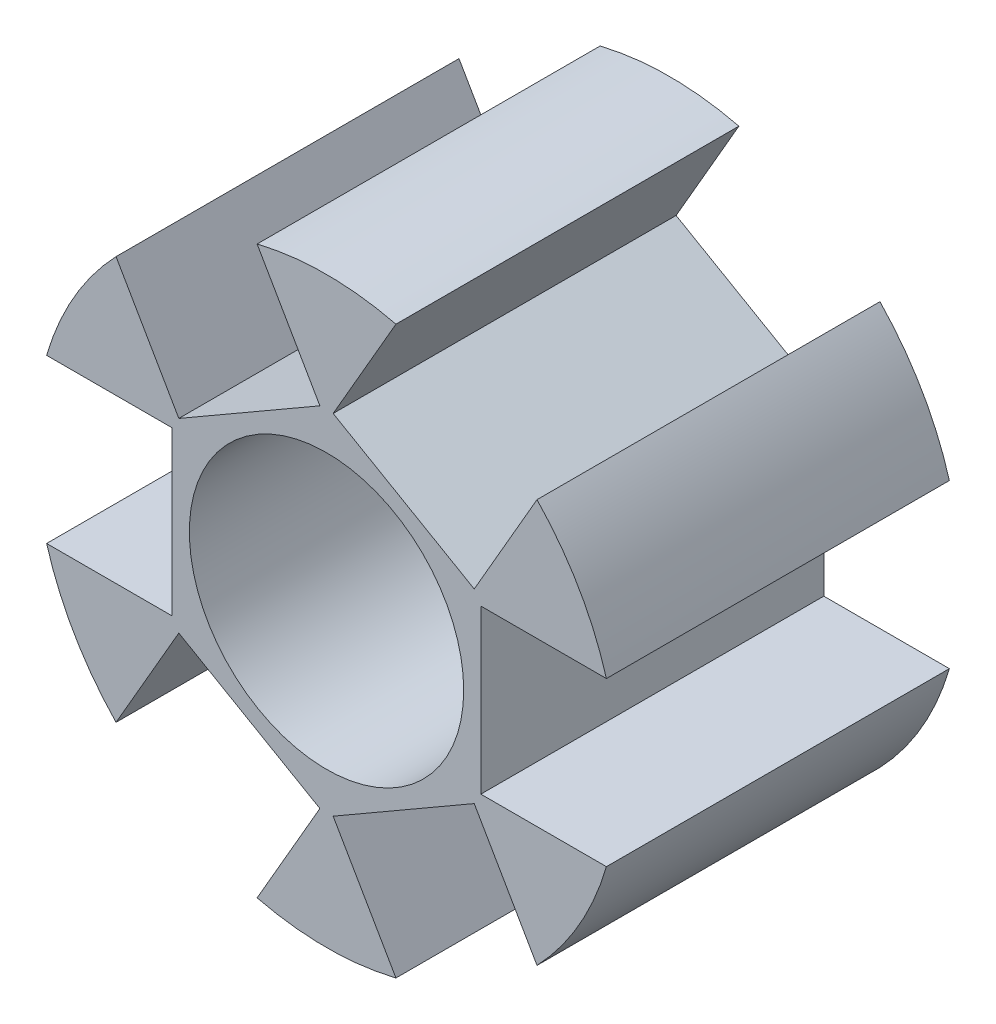
SolidWorks part; units mm, degrees
ref_plane "Top Plane" through (0, 0, 0) normal (0, 0, 1) x (1, 0, 0)
ref_plane "Right Plane" through (0, 0, 0) normal (0, 1, 0) x (1, 0, 0)
ref_plane "Front Plane" through (0, 0, 0) normal (1, 0, 0) x (0, 0, -1)
ref_axis "x-axis" through (-88.99, 0, 0) along (1, 0, 0)
ref_axis "y-axis" through (0, -55, 0) along (0, 1, 0)
ref_axis "z-axis" through (0, 0, 55) along (0, 0, -1)
sketch "Sketch1" plane through (0, 0, 0) normal (0, 0, 1) x (1, 0, 0)
  line L8 (-19.9785, 0) -> (0, 0) construction
  line L16 (0, 0) -> (0, -20.7846) construction
  line L23 (0, 0) -> (0, -20.7846) construction
  circle A0 centre (0, 0) radius 4
  circle A3 centre (0, 0) radius 8.5
  dimension "D1" = 8
  dimension "D2" = 17
extrude "Boss-Extrude1" add sketch "Sketch1" along normal mid plane 10
ref_plane "Plane1" through (-8.5, 0, 0) normal (-1, 0, 0) x (0, 0, 1)
sketch "Sketch2" plane through (-8.5, -17.1931, 0) normal (1, 0, 0) x (0, -1, 0)
  line L1 (-19.5681, -5) -> (-14.8181, -5)
  line L2 (-19.5681, -5) -> (-19.5681, 5)
  line L3 (-19.5681, 5) -> (-14.8181, 5)
  line L4 (-14.8181, -5) -> (-14.8181, 5)
  line L5 (-19.5681, -5) -> (-14.8181, 5) construction
  line L6 (-19.5681, 5) -> (-14.8181, -5) construction
  point P0 (-17.1931, 0)
  dimension "D1" = 4.75
  dimension "D2" = 10
extrude "Cut-Extrude3" cut sketch "Sketch2" along normal blind 4
pattern_circular "CirPattern1" count 6 over 360 about axis through (0, 0, 5) along (0, 0, 1) of "Cut-Extrude3"
